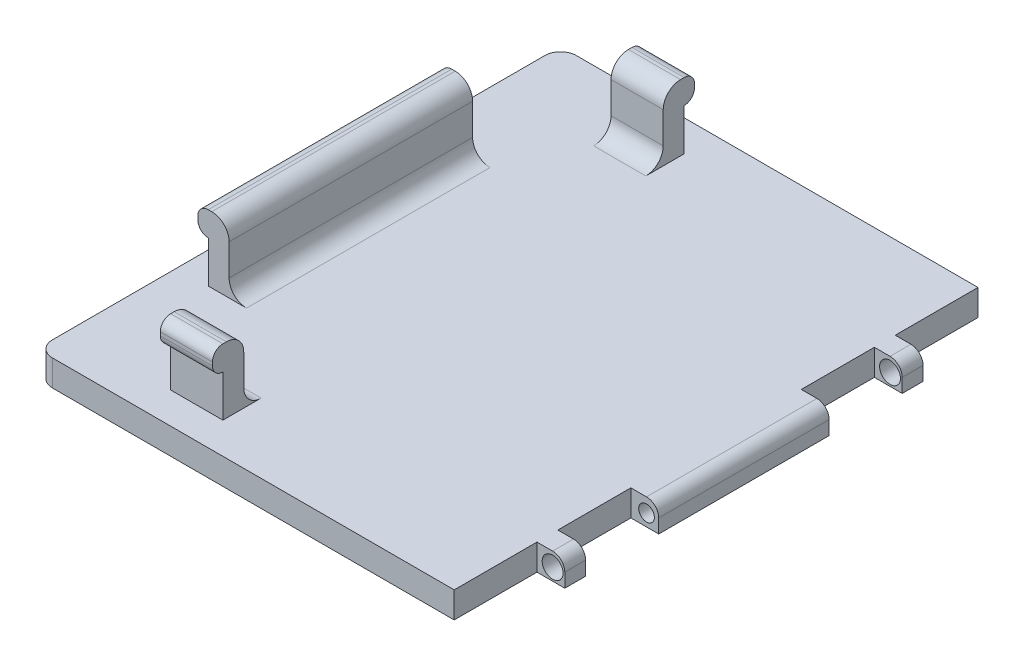
SolidWorks part; units mm, degrees
ref_plane "Front Plane" through (0, 0, 0) normal (0, 0, 1) x (1, 0, 0)
ref_plane "Top Plane" through (0, 0, 0) normal (0, 1, 0) x (1, 0, 0)
ref_plane "Right Plane" through (0, 0, 0) normal (1, 0, 0) x (0, 0, -1)
sketch "Sketch1" plane through (0, -10.0851, 0) normal (0, -1, 0) x (1, 0, 0)
  line L0 (56.8579, 38.1999) -> (56.8579, -32.5943)
  line L12 (53.3579, 36.9499) -> (53.3579, 25.3028)
  line L13 (53.3579, 25.3028) -> (56.8579, 25.3028)
  line L14 (56.8579, 25.3028) -> (56.8579, 38.1999)
  line L15 (54.6079, 40.4499) -> (-4.8921, 40.4499)
  line L16 (-7.1421, 38.1999) -> (-7.1421, -32.5943)
  line L17 (-4.8921, -34.8443) -> (54.6079, -34.8443)
  line L18 (56.8579, -32.5943) -> (56.8579, -19.6972)
  line L19 (56.8579, -19.6972) -> (53.3579, -19.6972)
  line L20 (53.3579, -19.6972) -> (53.3579, -31.3443)
  line L21 (53.3579, -31.3443) -> (-3.6421, -31.3443)
  line L22 (-3.6421, -31.3443) -> (-3.6421, 36.9499)
  line L23 (-3.6421, 36.9499) -> (53.3579, 36.9499)
  line L27 (54.6079, 40.4499) -> (-4.8921, 40.4499)
  line L28 (-7.1421, 38.1999) -> (-7.1421, -32.5943)
  line L29 (-4.8921, -34.8443) -> (54.6079, -34.8443)
  arc A4 (56.8579, 38.1999) -> (54.6079, 40.4499) centre (54.6079, 38.1999) ccw
  arc A5 (-4.8921, 40.4499) -> (-7.1421, 38.1999) centre (-4.8921, 38.1999) ccw
  arc A6 (-7.1421, -32.5943) -> (-4.8921, -34.8443) centre (-4.8921, -32.5943) ccw
  arc A7 (54.6079, -34.8443) -> (56.8579, -32.5943) centre (54.6079, -32.5943) ccw
  arc A8 (56.8579, 38.1999) -> (54.6079, 40.4499) centre (54.6079, 38.1999) ccw
  arc A9 (-4.8921, 40.4499) -> (-7.1421, 38.1999) centre (-4.8921, 38.1999) ccw
  arc A10 (-7.1421, -32.5943) -> (-4.8921, -34.8443) centre (-4.8921, -32.5943) ccw
  arc A11 (54.6079, -34.8443) -> (56.8579, -32.5943) centre (54.6079, -32.5943) ccw
  dimension "D1" = 0
extrude "Extrude Base" add sketch "Sketch1" along normal up to vertex (4 mm away) from offset 0.25
fillet "Fillet1" radius 1.75 1 edges at (56.8579, -10.3351, 2.8028)
sketch "Sketch2" plane through (0, -14.0851, 0) normal (0, -1, 0) x (1, 0, 0)
  line L0 (56.8579, 25.3028) -> (53.3579, 25.3028) construction
  line L1 (53.3579, 15.3028) -> (56.8579, 15.3028) construction
  line L2 (56.8579, -9.6972) -> (53.3579, -9.6972) construction
  line L3 (53.3579, -19.6972) -> (56.8579, -19.6972) construction
  line L4 (56.8579, 25.3028) -> (53.3579, 25.3028) construction
  line L5 (53.3579, 15.3028) -> (56.8579, 15.3028) construction
  line L6 (56.8579, -9.6972) -> (53.3579, -9.6972) construction
  line L7 (53.3579, -19.6972) -> (56.8579, -19.6972) construction
  line L9 (52.8579, 25.5528) -> (56.8579, 25.5528)
  line L10 (52.8579, 25.5528) -> (52.8579, 15.0528)
  line L11 (52.8579, 15.0528) -> (56.8579, 15.0528)
  line L12 (56.8579, 25.5528) -> (56.8579, 15.0528)
  line L13 (56.8579, -9.6972) -> (56.8579, 15.3028) construction
  line L15 (52.8579, -9.4472) -> (56.8579, -9.4472)
  line L16 (52.8579, -9.4472) -> (52.8579, -19.9472)
  line L17 (52.8579, -19.9472) -> (56.8579, -19.9472)
  line L18 (56.8579, -9.4472) -> (56.8579, -19.9472)
  line L19 (56.8579, -32.5943) -> (56.8579, -19.6972) construction
  line L20 (53.3579, -31.3443) -> (53.3579, 36.9499) construction
  line L21 (-4.8921, -34.8443) -> (54.6079, -34.8443) construction
  line L22 (52.8579, -22.9472) -> (56.8579, -22.9472)
  line L23 (52.8579, -22.9472) -> (52.8579, -34.8443)
  line L24 (52.8579, -34.8443) -> (56.8579, -34.8443)
  line L25 (56.8579, -22.9472) -> (56.8579, -34.8443)
  line L26 (54.6079, 40.4499) -> (-4.8921, 40.4499) construction
  line L27 (52.8579, 40.4499) -> (56.8579, 40.4499)
  line L28 (52.8579, 40.4499) -> (52.8579, 28.5528)
  line L29 (52.8579, 28.5528) -> (56.8579, 28.5528)
  line L30 (56.8579, 40.4499) -> (56.8579, 28.5528)
  dimension "D1" = 0.25
  dimension "D2" = 0.25
  dimension "D3" = 0.25
  dimension "D4" = 0.25
  dimension "D5" = 0.5
  dimension "D6" = 0.5
  dimension "D7" = 3
  dimension "D8" = 3
extrude "Cut-Extrude2" cut sketch "Sketch2" against normal through all
sketch "Sketch4" plane through (0, 0, -22.9472) normal (0, 0, -1) x (-1, 0, 0)
  circle A0 centre (-55.1079, -12.3351) radius 1.125 construction
  circle A1 centre (-55.1079, -12.3351) radius 1.125 construction
  circle A2 centre (-55.1079, -12.3351) radius 1.5
  dimension "D1" = 3
extrude "Cut-Extrude3" cut sketch "Sketch4" against normal through all
sketch "Sketch6" plane through (0, -10.3351, 0) normal (0, 1, 0) x (1, 0, 0)
  line L0 (-7.1421, -38.1999) -> (-7.1421, 32.5943) construction
  line L1 (-2.6421, -20.3028) -> (0.3579, -20.3028)
  line L2 (-2.6421, -20.3028) -> (-2.6421, 14.6972)
  line L3 (-2.6421, 14.6972) -> (0.3579, 14.6972)
  line L4 (0.3579, -20.3028) -> (0.3579, 14.6972)
  line L5 (-2.6421, -2.8028) -> (0.3579, -2.8028) construction
  line L6 (7.6079, 30.3443) -> (15.1079, 30.3443)
  line L7 (7.6079, 30.3443) -> (7.6079, 27.3443)
  line L8 (7.6079, 27.3443) -> (15.1079, 27.3443)
  line L9 (15.1079, 30.3443) -> (15.1079, 27.3443)
  line L10 (-4.8921, 34.8443) -> (52.8579, 34.8443) construction
  line L11 (15.1079, -35.9499) -> (15.1079, -32.9499)
  line L12 (7.6079, -32.9499) -> (15.1079, -32.9499)
  line L13 (7.6079, -35.9499) -> (7.6079, -32.9499)
  line L14 (7.6079, -35.9499) -> (15.1079, -35.9499)
  line L15 (6.3579, 31.3443) -> (16.3579, 31.3443) construction
  line L16 (6.3579, 31.3443) -> (16.3579, 31.3443)
  point P6 (-7.1421, -2.8028)
  point P7 (-2.6421, -2.8028)
  point P22 (11.3579, 30.3443)
  point P23 (11.3579, 31.3443)
  dimension "D2" = 35
  dimension "D1" = 4.5
  dimension "D3" = 3
  dimension "D4" = 4.5
  dimension "D6" = 3
  dimension "D7" = 7.5
extrude "Boss-Extrude2" add sketch "Sketch6" along normal blind 9.5 contours L5 L2 L1 L4 | L2 L5 L4 L3 | L9 L6 L7 L8 | L13 L14 L11 L12
sketch "Sketch7" plane through (0, 0, 20.3028) normal (0, 0, 1) x (1, 0, 0)
  line L1 (-2.6421, -0.8351) -> (-4.1421, -0.8351)
  line L2 (-2.6421, -0.8351) -> (-2.6421, -4.3351)
  line L3 (-2.6421, -4.3351) -> (-4.1421, -4.3351)
  line L4 (-4.1421, -0.8351) -> (-4.1421, -4.3351)
  dimension "D1" = 1.5
  dimension "D2" = 3.5
extrude "Boss-Extrude3" add sketch "Sketch7" against normal up to surface (35 mm away) up to face at (-1.1421, -5.5851, -14.6972)
sketch "Sketch8" plane through (15.1079, 0, 0) normal (1, 0, 0) x (0, 0, -1)
  line L1 (30.3443, -0.8351) -> (31.8443, -0.8351)
  line L2 (30.3443, -0.8351) -> (30.3443, -4.3351)
  line L3 (30.3443, -4.3351) -> (31.8443, -4.3351)
  line L4 (31.8443, -0.8351) -> (31.8443, -4.3351)
  dimension "D1" = 3.5
  dimension "D2" = 1.5
extrude "Boss-Extrude4" add sketch "Sketch8" against normal up to surface (7.5 mm away) up to face at (7.6079, -5.5851, -28.8443)
sketch "Sketch9" plane through (15.1079, 0, 0) normal (1, 0, 0) x (0, 0, -1)
  line L1 (-35.9499, -0.8351) -> (-37.4499, -0.8351)
  line L2 (-35.9499, -0.8351) -> (-35.9499, -4.3351)
  line L3 (-35.9499, -4.3351) -> (-37.4499, -4.3351)
  line L4 (-37.4499, -0.8351) -> (-37.4499, -4.3351)
  dimension "D1" = 1.5
  dimension "D2" = 3.5
extrude "Boss-Extrude5" add sketch "Sketch9" against normal up to surface (7.5 mm away) up to face at (7.6079, -5.5851, 34.4499)
fillet "Fillet2" radius 1.5 6 edges at (11.3579, -0.8351, -31.8443) (11.3579, -4.3351, -31.8443) (-4.1421, -0.8351, 2.8028) (-4.1421, -4.3351, 2.8028) (11.3579, -0.8351, 37.4499) (11.3579, -4.3351, 37.4499)
fillet "Fillet3" radius 2.5 6 edges at (11.3579, -10.3351, 32.9499) (11.3579, -10.3351, -27.3443) (0.3579, -10.3351, 2.8028) (11.3579, -0.8351, -27.3443) (0.3579, -0.8351, 2.8028) (11.3579, -0.8351, 32.9499)
sketch "Sketch11" plane through (0, 0, 15.0528) normal (0, 0, 1) x (1, 0, 0)
  circle A0 centre (55.1079, -12.3351) radius 1.5
  circle A1 centre (55.1079, -12.3351) radius 1.125
  circle A2 centre (55.1079, -12.3351) radius 1.5 construction
  dimension "D1" = 2.25
extrude "Boss-Extrude6" add sketch "Sketch11" against normal up to surface (24.5 mm away) up to face at (55.1079, -13.8351, -9.4472)
equation "\"D1@Extrude Base\" = \"cover thickness\""
equation "\"tolerance\"= 0.25"
equation "\"D1@Sketch2\"=\"tolerance\""
equation "\"D2@Sketch2\"=\"tolerance\""
equation "\"D3@Sketch2\"=\"tolerance\""
equation "\"D4@Sketch2\"=\"tolerance\""
equation "\"D5@Sketch2\"=\"tolerance\"*2"
equation "\"D6@Sketch2\"=\"tolerance\"*2"
equation "\"hinge fillet\" = 1.75"
equation "\"D1@Fillet1\"=\"hinge fillet\""
equation "\"D19@Extrude Base\"=\"tolerance\""
equation "\"hinge length\"= 3"
equation "\"hinge hole diameter\"= 3"
equation "\"D7@Sketch2\"=\"hinge length\""
equation "\"D8@Sketch2\"=\"hinge length\""
equation "\"D1@Sketch4\"=\"hinge hole diameter\""
equation "\"clip surface offset\" = 4.5"
equation "\"clip side offset\" = 15"
equation "\"clip height\"=5"
equation "\"front notch width\" = 35"
equation "\"D2@Sketch6\"=\"front notch width\""
equation "\"D1@Sketch6\"=\"clip surface offset\""
equation "\"notch wall depth\" = 3"
equation "\"D4@Sketch6\"=\"clip surface offset\""
equation "\"D6@Sketch6\"=\"notch wall depth\""
equation "\"side notch width\"= 7.5"
equation "\"D7@Sketch6\"=\"side notch width\""
equation "\"notch height\" = 9.5"
equation "\"D1@Boss-Extrude2\"=\"notch height\""
equation "\"notch depth\"=1.5"
equation "\"D1@Sketch7\"=\"notch depth\""
equation "\"notch\"=3.5"
equation "\"D1@Sketch8\"=\"notch\""
equation "\"D2@Sketch8\"=\"notch depth\""
equation "\"D2@Sketch7\"=\"notch\""
equation "\"D1@Sketch9\"=\"notch depth\""
equation "\"D2@Sketch9\"=\"notch\""
equation "\"notch fillet\"= 1.5"
equation "\"clip wall fillet\"= 2.5"
equation "\"D1@Fillet2\"=\"notch fillet\""
equation "\"D1@Fillet3\"=\"clip wall fillet\""
